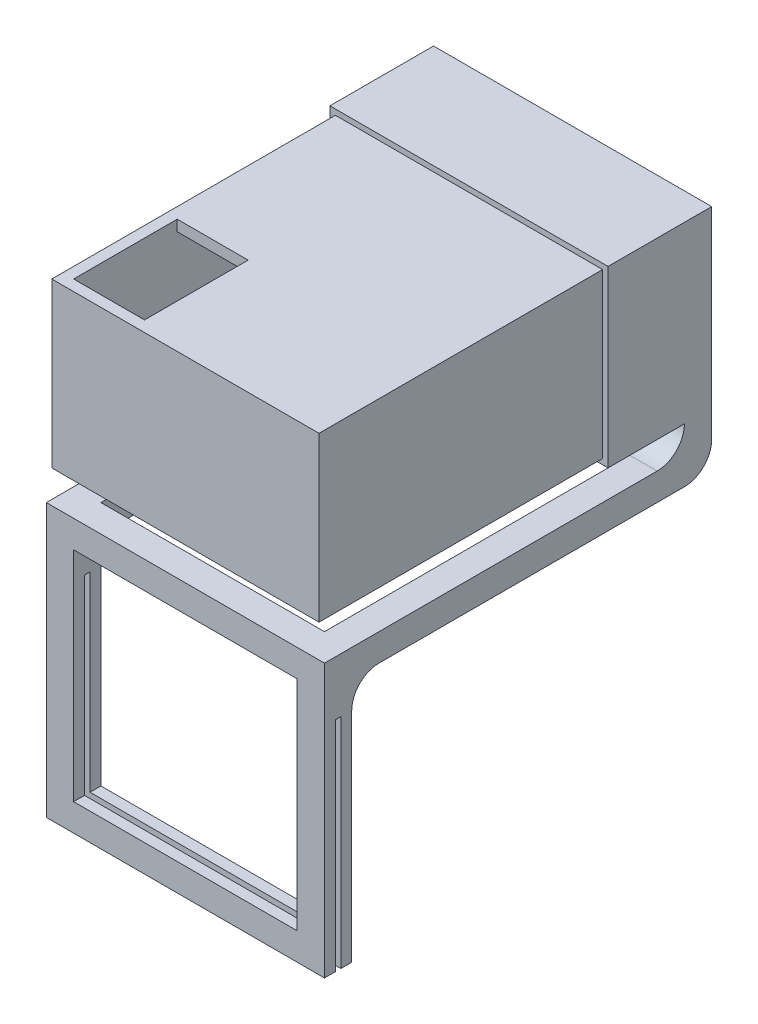
SolidWorks part; units mm, degrees
ref_plane "Front Plane" through (0, 0, 0) normal (0, 0, 1) x (1, 0, 0)
ref_plane "Top Plane" through (0, 0, 0) normal (0, 1, 0) x (1, 0, 0)
ref_plane "Right Plane" through (0, 0, 0) normal (1, 0, 0) x (0, 0, -1)
sketch "Esboço1" plane through (0, 0, 0) normal (0, 0, 1) x (1, 0, 0)
  line L0 (-25.5, 16) -> (-25.5, -16)
  line L1 (-22.5, 13) -> (22.5, 13)
  line L2 (-22.5, 13) -> (-22.5, -13)
  line L3 (-22.5, -13) -> (22.5, -13)
  line L4 (22.5, 13) -> (22.5, -13)
  line L5 (-22.5, 13) -> (22.5, -13) construction
  line L6 (-22.5, -13) -> (22.5, 13) construction
  line L7 (-22.5, -16) -> (22.5, -16)
  line L8 (25.5, 16) -> (25.5, -16)
  line L9 (-25.5, 16) -> (25.5, 16)
  line L25 (-25.5, -16) -> (25.5, -16) construction
  line L26 (25.5, -16) -> (22.5, -16)
  line L27 (-22.5, -16) -> (-25.5, -16)
  point P0 (0, 0)
  point P11 (0, 0)
  point P12 (-7.2898, -16)
  point P14 (-22.5, -16)
  dimension "D1" = 45
  dimension "D2" = 26
  dimension "D3" = 3
extrude "Ressalto-extrusão1" add sketch "Esboço1" along normal blind 5
sketch "Esboço6" plane through (0, 0, 0) normal (0, 0, -1) x (-1, 0, 0)
  line L0 (-22.5, -13) -> (-22.5, 13) construction
  line L1 (-22.5, 13) -> (22.5, 13) construction
  line L2 (22.5, 13) -> (22.5, -13) construction
  line L3 (22.5, -13) -> (-22.5, -13) construction
  line L4 (-22.5, -13) -> (-22.5, 13)
  line L5 (-22.5, 13) -> (22.5, 13)
  line L6 (22.5, 13) -> (22.5, -13)
  line L7 (22.5, -13) -> (-22.5, -13)
  line L9 (-25.5, -16) -> (25.5, -16)
  line L10 (-25.5, -16) -> (-25.5, 16)
  line L11 (-25.5, 16) -> (25.5, 16)
  line L12 (25.5, -16) -> (25.5, 16)
  line L13 (-25.5, -16) -> (25.5, 16) construction
  line L14 (-25.5, 16) -> (25.5, -16) construction
  point P2 (0, 0)
extrude "Ressalto-extrusão4" add sketch "Esboço6" against normal blind 14 from offset 5 offset against normal yes
sketch "Esboço7" plane through (0, 0, 19) normal (0, 0, 1) x (1, 0, 0)
  line L0 (-22.5, -13) -> (-22.5, 13) construction
  line L1 (-22.5, 13) -> (22.5, 13) construction
  line L2 (22.5, 13) -> (22.5, -13) construction
  line L3 (22.5, -13) -> (-22.5, -13) construction
  line L4 (-22.5, -13) -> (-22.5, 13)
  line L5 (-22.5, 13) -> (22.5, 13)
  line L6 (22.5, 13) -> (22.5, -13)
  line L7 (22.5, -13) -> (-22.5, -13)
  line L12 (24.5, 15) -> (24.5, -15)
  line L13 (24.5, -15) -> (-24.5, -15)
  line L14 (-24.5, -15) -> (-24.5, 15)
  line L15 (-24.5, 15) -> (24.5, 15)
  dimension "D1" = 2
extrude "Ressalto-extrusão5" add sketch "Esboço7" along normal blind 50
sketch "Esboço8" plane through (0, 0, 69) normal (0, 0, 1) x (1, 0, 0)
  line L4 (24.5, 15) -> (-24.5, 15)
  line L5 (-24.5, 15) -> (-24.5, -15)
  line L6 (-24.5, -15) -> (24.5, -15)
  line L7 (24.5, -15) -> (24.5, 15)
  line L8 (24.5, 15) -> (-24.5, 15)
  line L9 (-24.5, 15) -> (-24.5, -15)
  line L10 (-24.5, -15) -> (24.5, -15)
  line L11 (24.5, -15) -> (24.5, 15)
  dimension "D1" = 0
extrude "Ressalto-extrusão6" add sketch "Esboço8" along normal blind 2
sketch "Esboço10" plane through (0, 0, 69) normal (0, 0, -1) x (-1, 0, 0)
  line L0 (22.5, 0) -> (-8.5, 0) construction
  line L1 (22.5, 13) -> (22.5, -13) construction
  arc A4 (-2, 5.4772) -> (-2, -5.4772) centre (-8.5, 0) ccw
  arc A5 (-2, -5.4772) -> (-2, 5.4772) centre (4.5, 0) ccw
  dimension "D1" = 18
  dimension "D2" = 31
  dimension "D3" = 8.5
  dimension "D4" = 8.5
extrude "Ressalto-extrusão9" add sketch "Esboço10" along normal blind 15
sketch "Esboço11" plane through (0, 0, 54) normal (0, 0, -1) x (-1, 0, 0)
  circle A0 centre (-8.5, 0) radius 5.5
  circle A1 centre (4.5, 0) radius 5.5
  arc A2 (-2, -5.4772) -> (-2, 5.4772) centre (4.5, 0) ccw
  arc A3 (-2, 5.4772) -> (-2, -5.4772) centre (-8.5, 0) ccw
  arc A4 (-2, -5.4772) -> (-2, 5.4772) centre (4.5, 0) ccw
  arc A5 (-2, 5.4772) -> (-2, -5.4772) centre (-8.5, 0) ccw
  dimension "D2" = 11
  dimension "D3" = 11
  dimension "D1" = 0
extrude "Ressalto-extrusão10" add sketch "Esboço11" along normal blind 35
sketch "Esboço9" plane through (0, 15, 0) normal (0, 1, 0) x (1, 0, 0)
  line L0 (-16, -19.2951) -> (-16, -59.5) construction
  line L5 (-24.5, -71) -> (-24.5, -19) construction
  line L6 (24.5, -71) -> (-24.5, -71) construction
  line L10 (-9.5, -50) -> (-22.5, -50)
  line L11 (-9.5, -50) -> (-9.5, -69)
  line L12 (-9.5, -69) -> (-22.5, -69)
  line L13 (-22.5, -50) -> (-22.5, -69)
  line L14 (-9.5, -50) -> (-22.5, -69) construction
  line L15 (-9.5, -69) -> (-22.5, -50) construction
  point P0 (-16.3052, -40.2049)
  point P1 (0, 0)
  point P13 (-16, -59.5)
  dimension "D1" = 2
  dimension "D2" = 2
  dimension "D4" = 19
  dimension "D5" = 13
extrude "Corte-extrusão2" cut sketch "Esboço9" against normal blind 23
sketch "Esboço12" plane through (0, 0, 0) normal (0, 0, 1) x (1, 0, 0)
  line L1 (20.5, -21) -> (25.5, -21)
  line L2 (20.5, -21) -> (20.5, -16)
  line L3 (20.5, -16) -> (25.5, -16)
  line L4 (25.5, -21) -> (25.5, -16)
  line L5 (20.5, -21) -> (25.5, -16) construction
  line L6 (20.5, -16) -> (25.5, -21) construction
  line L7 (-20.5, -21) -> (-25.5, -21)
  line L8 (-20.5, -21) -> (-20.5, -16)
  line L9 (-20.5, -16) -> (-25.5, -16)
  line L10 (-25.5, -21) -> (-25.5, -16)
  line L11 (-20.5, -21) -> (-25.5, -16) construction
  line L12 (-20.5, -16) -> (-25.5, -21) construction
  point P0 (23, -18.5)
  point P5 (-23, -18.5)
  dimension "D1" = 5
  dimension "D2" = 5
  dimension "D3" = 5
  dimension "D4" = 5
extrude "Ressalto-extrusão11" add sketch "Esboço12" along normal blind 5
sketch "Esboço13" plane through (0, 0, 0) normal (0, 0, -1) x (-1, 0, 0)
  line L0 (25.5, -16) -> (25.5, -21) construction
  line L1 (25.5, -26) -> (20.5, -26)
  line L2 (25.5, -26) -> (25.5, -21)
  line L3 (25.5, -21) -> (20.5, -21)
  line L4 (20.5, -26) -> (20.5, -21)
  line L5 (25.5, -26) -> (20.5, -21) construction
  line L6 (25.5, -21) -> (20.5, -26) construction
  line L7 (-20.5, -26) -> (-25.5, -26)
  line L8 (-20.5, -26) -> (-20.5, -21)
  line L9 (-20.5, -21) -> (-25.5, -21)
  line L10 (-25.5, -26) -> (-25.5, -21)
  line L11 (-20.5, -26) -> (-25.5, -21) construction
  line L12 (-20.5, -21) -> (-25.5, -26) construction
  line L13 (-20.5, -16) -> (-20.5, -21) construction
  point P0 (23, -23.5)
  point P5 (-23, -23.5)
  dimension "D1" = 5
  dimension "D2" = 5
extrude "Ressalto-extrusão12" add sketch "Esboço13" against normal up to surface (71 mm away) up to face at (0, 0, 71)
sketch "Esboço14" plane through (0, 0, 71) normal (0, 0, 1) x (1, 0, 0)
  line L0 (25.5, -21) -> (25.5, -26) construction
  line L1 (25.5, -26) -> (-25.5, -26)
  line L2 (25.5, -26) -> (25.5, -21)
  line L3 (25.5, -21) -> (-25.5, -21)
  line L4 (-25.5, -26) -> (-25.5, -21)
  line L5 (25.5, -26) -> (-25.5, -21) construction
  line L6 (25.5, -21) -> (-25.5, -26) construction
  line L7 (-20.5, -26) -> (-25.5, -26) construction
  line L8 (-25.5, -26) -> (-25.5, -21) construction
  point P0 (0, -23.5)
  point P5 (25.5, -26)
  point P9 (-25.5, -26)
extrude "Ressalto-extrusão13" add sketch "Esboço14" against normal blind 5
sketch "Esboço16" plane through (-24.5, 0, 0) normal (-1, 0, 0) x (0, 0, 1)
  line L0 (29, -11) -> (19, -11) construction
  line L4 (19, 15) -> (19, -15) construction
  line L5 (71, -15) -> (19, -15) construction
  circle A0 centre (29, -11) radius 2
  dimension "D1" = 4
  dimension "D2" = 10
  dimension "D3" = 4
extrude "Corte-extrusão4" cut sketch "Esboço16" against normal blind 3
sketch "Esboço17" plane through (0, 0, 0) normal (1, 0, 0) x (0, 0, -1)
  line L0 (-54, 0) -> (-52.5, 0) construction
  line L1 (-54, -5.5) -> (-54, 5.5) construction
  circle A0 centre (-52.5, 0) radius 1.5
  point P6 (-51.6351, 0)
  dimension "D1" = 3
extrude "Corte-extrusão5" cut sketch "Esboço17" against normal mid plane 38
sketch "Esboço18" plane through (0, 0, 71) normal (0, 0, 1) x (1, 0, 0)
  line L0 (25.5, -21) -> (25.5, -26) construction
  line L1 (-25.5, -21) -> (25.5, -21)
  line L2 (-25.5, -21) -> (-25.5, -71)
  line L3 (-25.5, -71) -> (25.5, -71)
  line L4 (25.5, -21) -> (25.5, -71)
  line L5 (-20.5, -26) -> (-20.5, -66)
  line L6 (-20.5, -66) -> (20.5, -66)
  line L7 (20.5, -26) -> (20.5, -66)
  line L8 (-20.5, -26) -> (20.5, -26)
  point P4 (25.5, -21)
  dimension "D1" = 50
  dimension "D2" = 5
extrude "Ressalto-extrusão14" add sketch "Esboço18" against normal blind 5
fillet "Filete3" radius 5 6 edges at (-23, -26, 66) (23, -26, 66) (-23, -21, 5) (23, -21, 5) (-23, -26, 0) (23, -26, 0)
sketch "Esboço19" plane through (0, -71, 0) normal (0, -1, 0) x (1, 0, 0)
  line L0 (25.5, 68.5) -> (-25.5, 68.5) construction
  line L1 (25.5, 66) -> (25.5, 71) construction
  line L2 (-25.5, 66) -> (-25.5, 71) construction
  line L4 (25.5, 68) -> (-25.5, 68)
  line L5 (25.5, 68) -> (25.5, 69)
  line L6 (25.5, 69) -> (-25.5, 69)
  line L7 (-25.5, 68) -> (-25.5, 69)
  line L8 (25.5, 68) -> (-25.5, 69) construction
  line L9 (25.5, 69) -> (-25.5, 68) construction
  point P6 (0, 68.5)
  point P11 (-25.5, 69)
  dimension "D1" = 1
extrude "Corte-extrusão6" cut sketch "Esboço19" against normal blind 40
